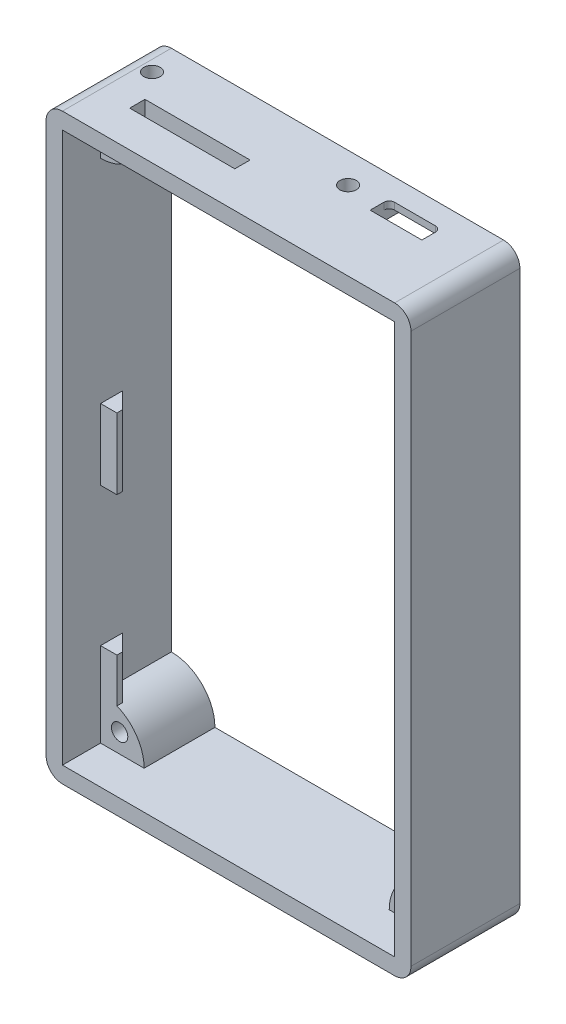
SolidWorks part; units mm, degrees
ref_plane "Přední rovina" through (0, 0, 0) normal (0, 0, 1) x (1, 0, 0)
ref_plane "Horní rovina" through (0, 0, 0) normal (0, 1, 0) x (1, 0, 0)
ref_plane "Pravá rovina" through (0, 0, 0) normal (1, 0, 0) x (0, 0, -1)
sketch "Skica1" plane through (0, 0, 0) normal (0, 0, 1) x (1, 0, 0)
  line L1 (0, 0) -> (61, 0)
  line L2 (0, 0) -> (0, 101)
  line L3 (0, 101) -> (61, 101)
  line L4 (61, 0) -> (61, 101)
  line L5 (-3, -3) -> (64, -3)
  line L6 (-3, -3) -> (-3, 104)
  line L7 (-3, 104) -> (64, 104)
  line L8 (64, -3) -> (64, 104)
  dimension "D1" = 61
  dimension "D2" = 101
  dimension "D3" = 3
  dimension "D4" = 3
  dimension "D5" = 3
  dimension "D6" = 3
extrude "Přidat vysunutím1" add sketch "Skica1" along normal blind 7
sketch "Skica2" plane through (0, 0, 0) normal (0, 0, -1) x (-1, 0, 0)
  line L1 (-64, 104) -> (3, 104)
  line L2 (-64, 104) -> (-64, -3)
  line L3 (-64, -3) -> (3, -3)
  line L4 (3, 104) -> (3, -3)
  line L5 (-61, 101) -> (0, 101)
  line L6 (-61, 101) -> (-61, 0)
  line L7 (-61, 0) -> (0, 0)
  line L8 (0, 101) -> (0, 0)
  arc A0 (-7.4162, 104) -> (3, 93.5838) centre (0, 101) ccw
  arc A1 (3, 7.4162) -> (-7.4162, -3) centre (0, 0) ccw
  arc A2 (-53.5838, -3) -> (-64, 7.4162) centre (-61, 0) ccw
  arc A3 (-64, 93.5838) -> (-53.5838, 104) centre (-61, 101) ccw
  line M1 (3, -3) -> (3, 104)
  line M2 (3, 104) -> (-64, 104)
  line M3 (-64, 104) -> (-64, -3)
  line M4 (-64, -3) -> (3, -3)
  line M5 (-61, 101) -> (0, 101)
  line M6 (0, 101) -> (0, 0)
  line M7 (0, 0) -> (-61, 0)
  line M8 (-61, 0) -> (-61, 101)
  dimension "D1" = 16
  dimension "D2" = 16
  dimension "D3" = 16
  dimension "D4" = 16
extrude "Přidat vysunutím2" add sketch "Skica2" along normal blind 13 contours A2 L3 A1 L7 | A2 L2 M8 M4 M7 | A2 M7 M8 | A3 L2 A2 L6 | A3 M5 M2 M3 M8 | A3 M8 M5 | A3 L5 A0 L1 | A0 L5 L4 M2 M6 | L5 A0 M6 | A1 L4 A0 L8 | A1 L3 M1 M6 M7 | A1 M6 M7 region at (58.7919, 103.8444, 0) region at (30.5, 102.5064, 0) region at (62.5034, 50.5, 0) region at (2.2081, 103.8444, 0) region at (57.6047, 97.6047, 0) region at (62.4984, 7.7, 0) region at (3.3953, 97.6047, 0) region at (57.6047, 3.3953, 0) region at (-1.5034, 50.5, 0) region at (30.5, -1.5064, 0) region at (-2.8444, 2.2081, 0) region at (3.3953, 3.3953, 0)
sketch "Skica3" plane through (0, 0, 0) normal (0, 0, 1) x (1, 0, 0)
  line L0 (3.5, 97.5) -> (3.5, 3.5) construction
  line L1 (0, 101) -> (0, 0) construction
  line L2 (3.5, 3.5) -> (57.5, 3.5) construction
  line L3 (0, 0) -> (61, 0) construction
  circle A0 centre (3.5, 97.5) radius 1.5
  circle A1 centre (3.5, 3.5) radius 1.5
  circle A2 centre (57.5, 3.5) radius 1.5
  circle A3 centre (57.5, 97.5) radius 1.5
  point P8 (0, 50.5)
  point P9 (3.5, 50.5)
  point P10 (30.5, 3.5)
  point P13 (30.5, 0)
  dimension "D3" = 3
  dimension "D4" = 3
  dimension "D5" = 3
  dimension "D6" = 3
  dimension "D1" = 54
  dimension "D2" = 94
extrude "Odebrat vysunutím1" cut sketch "Skica3" against normal blind 13
sketch "Skica4" plane through (0, 0, -13) normal (0, 0, -1) x (-1, 0, 0)
  line L0 (-53, 101) -> (-61, 101)
  line L1 (-61, 101) -> (-61, 93)
  arc A0 (-61, 93) -> (-53, 101) centre (-61, 101) ccw
extrude "Odebrat vysunutím2" cut sketch "Skica4" against normal blind 4.8
sketch "Skica8" plane through (0, 0, 0) normal (0, 0, 1) x (1, 0, 0)
  line L0 (0, 101) -> (8, 101)
  line L1 (0, 101) -> (0, 93)
  line L2 (3.5, 94.5) -> (0, 94.5)
  line L3 (6.5, 97.5) -> (6.5, 101)
  line L4 (57.5, 94.75) -> (61, 94.75)
  line L7 (61, 93) -> (61, 101) construction
  line L8 (54.75, 97.5) -> (54.75, 101)
  line L9 (61, 101) -> (53, 101) construction
  circle A0 centre (57.5, 97.5) radius 2.75
  circle A1 centre (61, 101) radius 8
  circle A2 centre (0, 101) radius 8
  circle A3 centre (3.5, 97.5) radius 3
  arc A7 (0, 93) -> (8, 101) centre (0, 101) ccw construction
  arc A9 (53, 101) -> (61, 93) centre (61, 101) ccw construction
  circle A10 centre (57.5, 97.5) radius 1.5 construction
  circle A11 centre (3.5, 97.5) radius 1.5 construction
  line M7 (61, 93) -> (61, 101)
  line M8 (61, 101) -> (53, 101)
  arc M9 (53, 101) -> (61, 93) centre (61, 101) ccw
  dimension "D1" = 6
  dimension "D2" = 5.5
extrude "Odebrat vysunutím4" cut sketch "Skica8" against normal through all contours A0 L8 L4 M8 M9 M7 region at (59.25, 94.6369, 0)
fillet "Zaoblit1" radius 3 4 edges at (-3, 104, -3) (64, 104, -3) (64, -3, -3) (-3, -3, -3)
sketch "Skica5" plane through (0, 0, 0) normal (1, 0, 0) x (0, 0, -1)
  line L0 (-7, 0) -> (0, 0) construction
  line L1 (0, 7) -> (4, 7)
  line L2 (0, 7) -> (0, 15.5)
  line L3 (0, 15.5) -> (4, 15.5)
  line L4 (4, 7) -> (4, 15.5)
  line L5 (0, 41) -> (4, 41)
  line L6 (0, 41) -> (0, 54)
  line L7 (0, 54) -> (4, 54)
  line L8 (4, 41) -> (4, 54)
  line L9 (0, 8) -> (0, 0) construction
  dimension "D1" = 8.5
  dimension "D2" = 13
  dimension "D3" = 41
  dimension "D4" = 4
  dimension "D5" = 7
extrude "Přidat vysunutím3" add sketch "Skica5" along normal blind 3
chamfer "Zkosení1" distance 3 angle 45 2 edges at (3, 11.4581, -4) (3, 47.5, -4)
sketch "Skica6" plane through (61, 0, 0) normal (-1, 0, 0) x (0, 0, 1)
  line L0 (0, 0) -> (0, 8) construction
  line L1 (0, 7) -> (-4, 7)
  line L2 (0, 7) -> (0, 15.5)
  line L3 (0, 15.5) -> (-4, 15.5)
  line L4 (-4, 7) -> (-4, 15.5)
  line L5 (7, 0) -> (0, 0) construction
  line L6 (0, 41) -> (-4, 41)
  line L7 (0, 41) -> (0, 54)
  line L8 (0, 54) -> (-4, 54)
  line L9 (-4, 41) -> (-4, 54)
  dimension "D1" = 4
  dimension "D2" = 8.5
  dimension "D3" = 7
  dimension "D4" = 13
  dimension "D5" = 41
extrude "Přidat vysunutím4" add sketch "Skica6" along normal blind 3
chamfer "Zkosení2" distance 3 angle 45 2 edges at (58, 11.4581, -4) (58, 47.5, -4)
sketch "Skica7" plane through (0, 104, 0) normal (0, 1, 0) x (1, 0, 0)
  line L2 (53.5, 13) -> (53.5, 5.5)
  line L3 (53.5, 5.5) -> (44, 5.5)
  line L4 (44, 13) -> (44, 5.5)
  line L5 (61, -7) -> (61, 13) construction
  line L7 (44, 13) -> (53.5, 13)
  line L11 (0, 13) -> (61, 13) construction
  dimension "D1" = 9.5
  dimension "D2" = 7.5
  dimension "D4" = 7.5
extrude "Odebrat vysunutím3" cut sketch "Skica7" against normal blind 10
sketch "Skica9" plane through (0, 0, -13) normal (0, 0, -1) x (-1, 0, 0)
  line L0 (-44, 101) -> (-44, 104) construction
  line L1 (-53.5, 104) -> (-44, 104)
  line L2 (-53.5, 104) -> (-53.5, 102.75)
  line L3 (-53.5, 102.75) -> (-44, 102.75)
  line L4 (-44, 104) -> (-44, 102.75)
  dimension "D1" = 1.25
extrude "Přidat vysunutím5" add sketch "Skica9" against normal blind 4
fillet "Zaoblit2" radius 1 2 edges at (53.5, 103.375, -9) (44, 103.375, -9)
sketch "Skica10" plane through (0, 101, 0) normal (0, -1, 0) x (1, 0, 0)
  line L0 (0, 7) -> (0, 0) construction
  line L1 (5.7, 0.35) -> (25, 0.35)
  line L2 (5.7, 0.35) -> (5.7, -2.45)
  line L3 (5.7, -2.45) -> (25, -2.45)
  line L4 (25, 0.35) -> (25, -2.45)
  line L6 (8, 0) -> (0, 0) construction
  dimension "D1" = 5.7
  dimension "D2" = 19.3
  dimension "D3" = 2.8
  dimension "D4" = 0.35
extrude "Odebrat vysunutím5" cut sketch "Skica10" against normal mid plane 12
sketch "Skica11" plane through (0, 104, 0) normal (0, 1, 0) x (1, 0, 0)
  line L0 (0, 13) -> (0, -7) construction
  line L1 (44, 8) -> (44, 5.5) construction
  line L2 (5.7, 2.45) -> (25, 2.45) construction
  circle A0 centre (2, 7.45) radius 1.5
  circle A1 centre (38, 7.45) radius 1.5
  point P4 (0, 0)
  dimension "D1" = 3
  dimension "D2" = 3
  dimension "D3" = 2
  dimension "D4" = 6
  dimension "D5" = 5
extrude "Odebrat vysunutím6" cut sketch "Skica11" against normal blind 4 contours A1 | A0 region at (38, 104, -7.45)
sketch "Skica13" plane through (0, 101, 0) normal (0, -1, 0) x (1, 0, 0)
  circle A0 centre (38, -7.45) radius 2.5
  circle A1 centre (38, -7.45) radius 1.5 construction
  dimension "D1" = 1
extrude "Přidat vysunutím6" add sketch "Skica13" along normal blind 1
